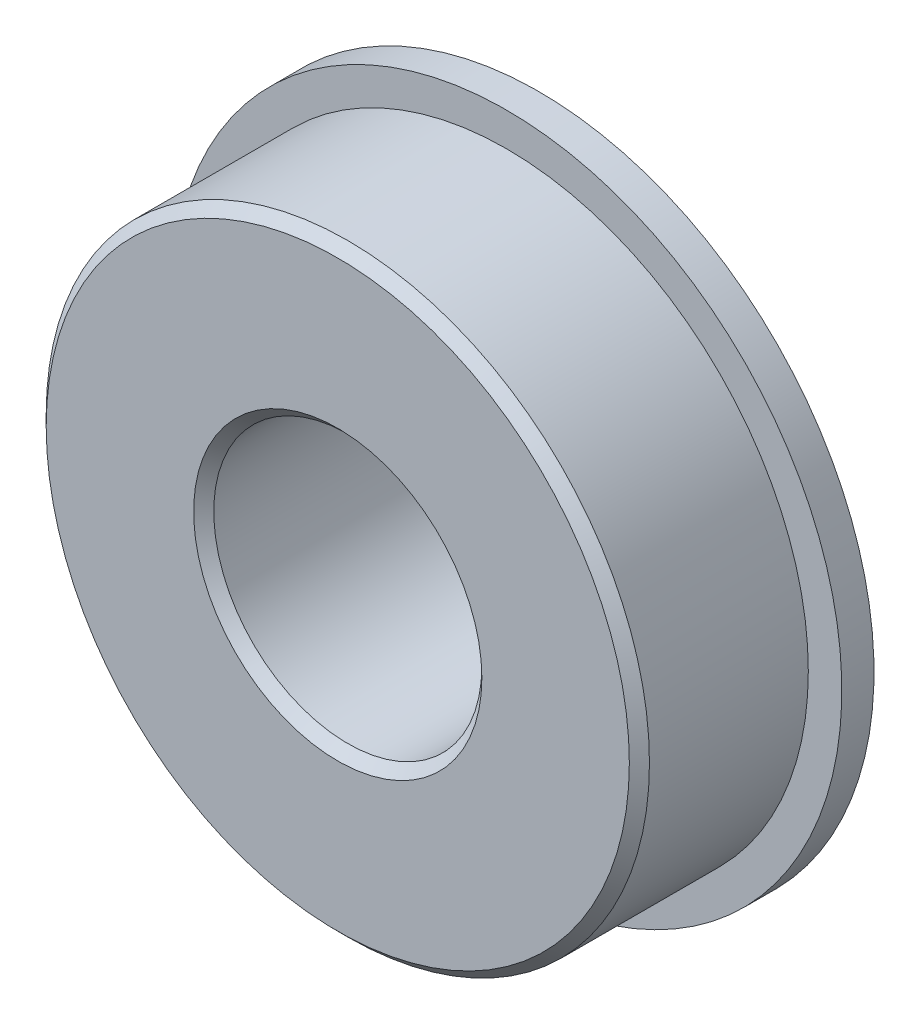
SolidWorks part; units mm, degrees
ref_plane "Front Plane" through (0, 0, 0) normal (0, 0, 1) x (1, 0, 0)
ref_plane "Top Plane" through (0, 0, 0) normal (0, 1, 0) x (1, 0, 0)
ref_plane "Right Plane" through (0, 0, 0) normal (1, 0, 0) x (0, 0, -1)
sketch "Sketch1" plane through (0, 0, 0) normal (1, 0, 0) x (0, 0, -1)
  line L0 (-4.7625, 0) -> (4.7625, 0) construction
  line L1 (0, 14.2875) -> (0, -14.2875) construction
  line L2 (4.2863, 14.2875) -> (-4.2862, 14.2875)
  line L3 (-4.2862, 14.2875) -> (-4.7625, 13.8112)
  line L4 (-4.7625, 13.8112) -> (-4.7625, 10.7188)
  line L5 (-4.7625, 10.7188) -> (-2.3474, 10.7188)
  line L6 (4.7625, 10.7188) -> (2.3474, 10.7188)
  line L7 (4.7625, 13.8113) -> (4.7625, 10.7188)
  line L8 (4.2863, 14.2875) -> (4.7625, 13.8113)
  line L9 (0, 14.2875) -> (0, 10.3187) construction
  line L10 (0, 10.3187) -> (0, 6.35) construction
  line L11 (4.7625, 8.7376) -> (4.7625, -8.7376) construction
  line L12 (-4.7625, 6.35) -> (4.7625, 6.35) construction
  line L13 (0, 7.9375) -> (0, 6.35) construction
  line L14 (0, 12.7) -> (0, 14.2875) construction
  line L15 (4.7625, 8.7376) -> (0, 8.7376) construction
  circle A1 centre (0, 10.3187) radius 2.3813 construction
  arc A2 (-2.3474, 10.7188) -> (2.3474, 10.7188) centre (0, 10.3187) cw
  point P14 (0, 6.35)
  point P22 (0, 7.9375)
  point P23 (0, 12.7)
  dimension "D3" = 4.7625
  dimension "Width" = 9.525
  dimension "OD" = 28.575
  dimension "D1" = 45
  dimension "D2" = 0.4763
  dimension "D4" = 17.4752
  dimension "D5" = 3.9624
  dimension "D6" = 1.9812
revolve "Revolve1" add sketch "Sketch1" angle 360 about L0
sketch "Sketch3" plane through (0, 0, 0) normal (1, 0, 0) x (0, 0, -1)
  line L1 (-4.7625, 13.8112) -> (-4.7625, 10.7188) construction
  line L2 (-4.2862, 14.2875) -> (-4.7625, 13.8112) construction
  line L3 (-4.7625, 9.9187) -> (-4.7625, 6.8262) construction
  line L4 (-4.7625, 6.8262) -> (-4.7625, 8.2614)
  line L5 (-4.7625, 6.8262) -> (-4.2863, 6.35)
  line L6 (-4.2863, 6.35) -> (5.8865, 6.35)
  line L7 (-4.7625, 13.8112) -> (-4.7625, -13.8112) construction
  line L8 (5.8865, 6.35) -> (6.3627, 6.8262)
  line L9 (0, 0) -> (6.3627, 0) construction
  line L13 (4.2863, 14.2875) -> (4.7625, 13.8113) construction
  line L14 (-4.7625, 8.2614) -> (-4.2863, 8.7376)
  line L15 (-4.2863, 8.7376) -> (-1.7805, 8.7376)
  line L16 (1.7805, 8.7376) -> (5.8864, 8.7376)
  line L17 (5.8864, 8.7376) -> (6.3627, 8.2614)
  line L18 (6.3627, 8.2614) -> (6.3627, 6.8262)
  circle A0 centre (0, 10.3187) radius 2.3812 construction
  arc A1 (-1.7805, 8.7376) -> (1.7805, 8.7376) centre (0, 10.3187) ccw
  dimension "D1" = 45
  dimension "Ring Wd" = 11.1252
  dimension "Inner Ring OD" = 17.4752
revolve "Revolve3" add sketch "Sketch3" angle 360 about L0
sketch "Sketch6" plane through (0, 0, 0) normal (1, 0, 0) x (0, 0, -1)
  line L1 (4.7625, 10.7188) -> (3.2385, 10.7188)
  line L2 (4.7625, 10.7188) -> (4.7625, 15.875)
  line L3 (4.7625, 15.875) -> (3.2385, 15.875)
  line L4 (3.2385, 10.7188) -> (3.2385, 15.875)
  line L5 (4.7625, 0) -> (-4.7625, 0) construction
  dimension "Flange OD" = 31.75
  dimension "Flange Thickness" = 1.524
revolve "Revolve6" add sketch "Sketch6" angle 360 about L5
sketch "Sketch4" plane through (0, 0, 0) normal (1, 0, 0) x (0, 0, -1)
  line L0 (-2.3813, 10.3187) -> (2.3813, 10.3187)
  circle A0 centre (0, 10.3187) radius 2.3812 construction
  arc A1 (2.3813, 10.3187) -> (-2.3813, 10.3187) centre (0, 10.3187) ccw
revolve "Revolve4" add sketch "Sketch4" angle 360 about L0
ref_axis "Axis1" through (0, 0, -4.7625) along (0, 0, 1)
pattern_circular "CirPattern1" count 12 every 30 about axis through (0, 0, -4.7625) along (0, 0, 1) of bodies 104
sketch "Sketch5" plane through (0, 0, 0) normal (1, 0, 0) x (0, 0, -1)
  line L0 (-4.7625, 10.7188) -> (-2.3474, 10.7188) construction
  line L1 (-4.5244, 10.7188) -> (-1.7805, 10.7188)
  line L2 (-4.5244, 10.7188) -> (-4.5244, 8.7376)
  line L3 (-4.5244, 8.7376) -> (-1.7805, 8.7376)
  line L4 (-1.7805, 10.7188) -> (-1.7805, 8.7376)
  line L6 (4.7625, 10.7188) -> (2.3474, 10.7188) construction
  line L7 (4.5244, 10.7188) -> (1.7805, 10.7188)
  line L8 (4.5244, 10.7188) -> (4.5244, 8.7376)
  line L9 (4.5244, 8.7376) -> (1.7805, 8.7376)
  line L10 (1.7805, 10.7188) -> (1.7805, 8.7376)
  line L12 (-4.2862, 14.2875) -> (-4.7625, 13.8112) construction
  line L13 (4.7625, 8.7376) -> (0, 8.7376) construction
  line L15 (-4.2863, 8.7376) -> (-1.7805, 8.7376) construction
  line L16 (4.5244, 10.7188) -> (4.5244, 14.0494) construction
  line L17 (4.2863, 14.2875) -> (4.7625, 13.8113) construction
  point P18 (-4.5244, 14.0494)
revolve "Revolve5" [suppressed] add sketch "Sketch5" angle 360 about L0
sketch "Sketch7" plane through (0, 0, 4.7625) normal (0, 0, 1) x (1, 0, 0)
  circle A0 centre (0, 0) radius 13.8112
  circle A1 centre (0, 0) radius 6.8262 construction
  circle A2 centre (0, 0) radius 6.8262
extrude "Boss-Extrude1" add sketch "Sketch7" against normal up to surface (9.525 mm away)
equation "\"D2@Sketch1\" = \"Width@Sketch1\"*.05"
equation "\"D2@CirPattern1\" = 360/\"Balls@CirPattern1\""
equation "\"D4@Sketch1\"=\"Inner Ring OD@Sketch3\""
equation "\"D3@Sketch1\"=\"Width@Sketch1\"/2."
equation "\"D6@Sketch1\"=\"D5@Sketch1\"/2"
